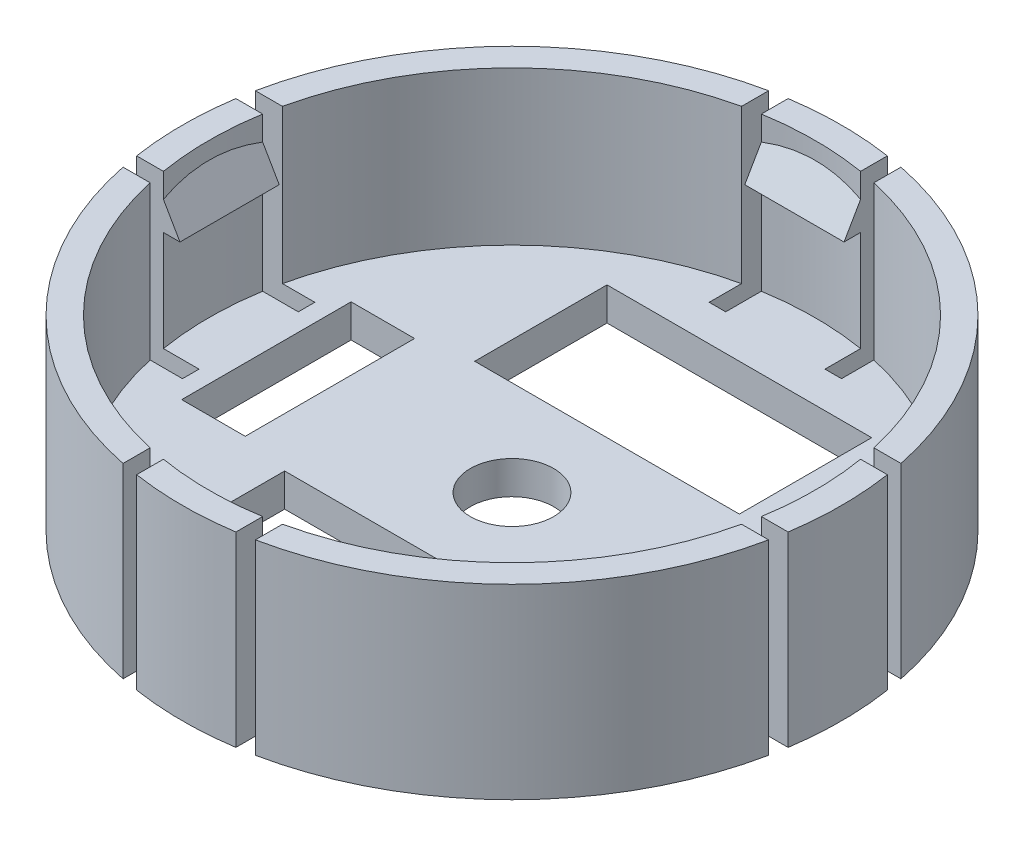
SolidWorks part; units mm, degrees
ref_plane "Front Plane" through (0, 0, 0) normal (0, 0, 1) x (1, 0, 0)
ref_plane "Top Plane" through (0, 0, 0) normal (0, 1, 0) x (1, 0, 0)
ref_plane "Right Plane" through (0, 0, 0) normal (1, 0, 0) x (0, 0, -1)
sketch "Sketch1" plane through (0, 0, 0) normal (0, 1, 0) x (1, 0, 0)
  circle A0 centre (0, 0) radius 15.8115
  circle A1 centre (0, 0) radius 14.5415
  dimension "D1" = 29.083
  dimension "D2" = 1.27
extrude "Boss-Extrude1" add sketch "Sketch1" along normal blind 1.5875 contours A0
extrude "Boss-Extrude2" add sketch "Sketch1<3>" along normal blind 7.366 from surface starting at face at (0, 1.5875, 15.8115)
sketch "Sketch1<3>" plane through (0, 0, 0) normal (0, 1, 0) x (1, 0, 0) same geometry as "Sketch1"
sketch "Sketch3" plane through (0, 8.9535, 0) normal (0, 1, 0) x (1, 0, 0)
  line L0 (-2.3813, 15.8115) -> (2.3813, 15.8115) construction
  line L1 (3.175, 15.8115) -> (2.3813, 15.8115)
  line L2 (3.175, 15.8115) -> (3.175, 12.6365)
  line L3 (3.175, 12.6365) -> (2.3813, 12.6365)
  line L4 (2.3813, 15.8115) -> (2.3813, 12.6365)
  line L5 (-2.3813, 15.8115) -> (-3.175, 15.8115)
  line L6 (-2.3813, 15.8115) -> (-2.3813, 12.6365)
  line L7 (-2.3813, 12.6365) -> (-3.175, 12.6365)
  line L8 (-3.175, 15.8115) -> (-3.175, 12.6365)
  circle A0 centre (0, 0) radius 15.8115 construction
  point P8 (0, 0)
  point P11 (0, 15.8115)
  dimension "D1" = 4.7625
  dimension "D2" = 0.7937
  dimension "D3" = 3.175
extrude "Cut-Extrude1" cut sketch "Sketch3" against normal up to surface (8.9535 mm away) up to face at (0, 0, 15.8115)
sketch "Sketch4" plane through (0, 0, 0) normal (-1, 0, 0) x (0, 0, 1)
  line L0 (-15.6312, 8.9535) -> (-15.6312, 6.4135)
  line L1 (-15.6312, 0) -> (-15.6312, 8.9535) construction
  line L2 (-15.6312, 6.4135) -> (-13.5515, 6.4135)
  line L3 (-13.5515, 6.4135) -> (-15.0179, 8.9535)
  line L4 (-15.6312, 8.9535) -> (-15.0179, 8.9535)
  line L5 (-14.3452, 8.9535) -> (-15.6312, 8.9535) construction
  line L6 (-14.3452, 8.9535) -> (-14.5415, 8.9535) construction
  line L7 (-14.3452, 8.9535) -> (-14.5415, 8.9535) construction
  line L9 (-14.3452, 1.5875) -> (-14.3452, 8.9535) construction
  line L10 (-12.6365, 1.5875) -> (-14.3452, 1.5875) construction
  dimension "D1" = 30
  dimension "D2" = 4.826
  dimension "D3" = 0.7937
extrude "Boss-Extrude3" add sketch "Sketch4" against normal mid plane 4.7625
pattern_circular "CirPattern2" count 4 over 360 about axis through (0, 1.5875, 0) along (0, -1, 0) of "Cut-Extrude1", "Boss-Extrude3"
sketch "Sketch5" plane through (0, 1.5875, 0) normal (0, 1, 0) x (1, 0, 0)
  line L0 (-6.35, 4.5593) -> (-6.35, -4.5593) construction
  line L1 (6.35, 10.9093) -> (-6.35, 10.9093)
  line L2 (6.35, 10.9093) -> (6.35, 4.5593)
  line L3 (6.35, 4.5593) -> (-6.35, 4.5593)
  line L4 (-6.35, 10.9093) -> (-6.35, 4.5593)
  line L5 (6.35, -4.5593) -> (-6.35, -4.5593)
  line L6 (6.35, -4.5593) -> (6.35, -10.9093)
  line L7 (6.35, -10.9093) -> (-6.35, -10.9093)
  line L8 (-6.35, -4.5593) -> (-6.35, -10.9093)
  line L10 (-8.7376, 4.064) -> (-11.7856, 4.064)
  line L11 (-8.7376, 4.064) -> (-8.7376, -4.064)
  line L12 (-8.7376, -4.064) -> (-11.7856, -4.064)
  line L13 (-11.7856, 4.064) -> (-11.7856, -4.064)
  circle A0 centre (0, 0) radius 2
  point P8 (0, 4.5593)
  point P9 (6.35, 7.7343)
  point P11 (-6.35, 0)
  point P12 (6.35, -7.7343)
  point P17 (-8.7376, 0)
  point P18 (-10.2616, 4.064)
  dimension "D7" = 4
  dimension "D1" = 6.35
  dimension "D2" = 12.7
  dimension "D3" = 15.4686
  dimension "D4" = 8.128
  dimension "D5" = 3.048
  dimension "D6" = 10.2616
extrude "Cut-Extrude2" cut sketch "Sketch5" against normal through all
